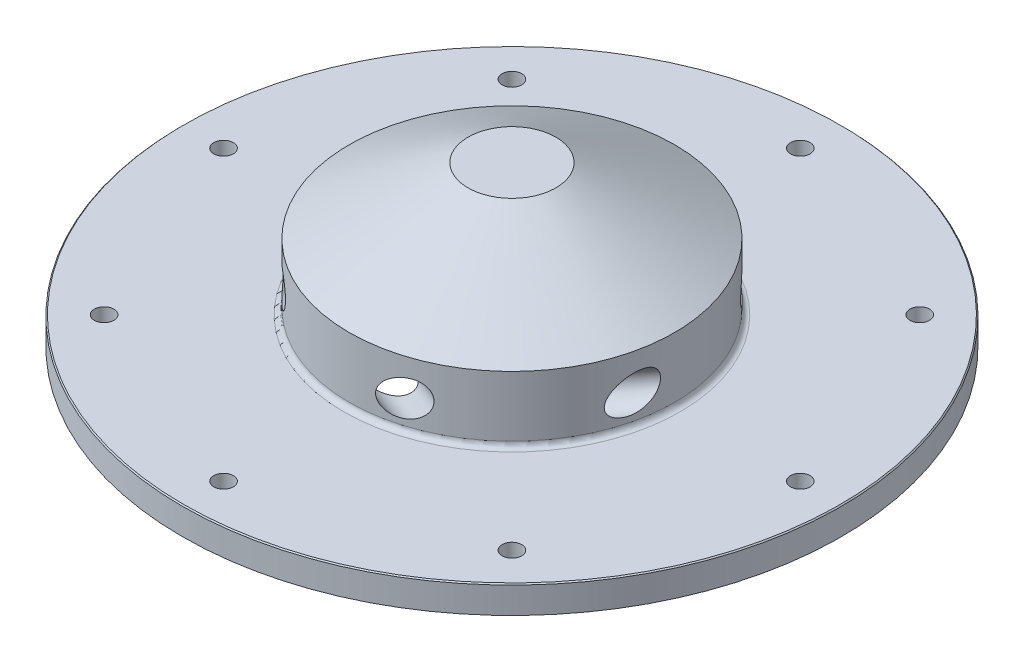
SolidWorks part; units mm, degrees
material "7075-T6 (SN)"
ref_plane "Front Plane" through (0, 0, 0) normal (0, 0, 1) x (1, 0, 0)
ref_plane "Top Plane" through (0, 0, 0) normal (0, 1, 0) x (1, 0, 0)
ref_plane "Right Plane" through (0, 0, 0) normal (1, 0, 0) x (0, 0, -1)
sketch "Sketch2" plane through (0, 0, 0) normal (0, 1, 0) x (1, 0, 0)
  circle A0 centre (0, 0) radius 38.1
  dimension "D1" = 76.2
extrude "Boss-Extrude1" add sketch "Sketch2" along normal blind 3.175
hole_wizard "Tap Drill for #4-40 Tap1" positions "Sketch3" profile "Sketch4" hole size "#4-40" standard "ANSI Inch" end condition through all
sketch "Sketch3" plane through (0, 0, 0) normal (0, -1, 0) x (-1, 0, 0)
  point P0 (0, -33.3375)
  dimension "D1" = 33.3375
sketch "Sketch4" plane through (0, 0, 33.3375) normal (1, 0, 0) x (0, 0, -1)
  line L0 (0, 0) -> (0, 3.175)
  line L1 (0, 3.175) -> (1.1303, 3.175)
  line L2 (1.1303, 3.175) -> (1.1303, 0)
  line L5 (1.1303, 0) -> (0, 0)
  line L11 (0, -6.35) -> (0, 107.95) construction
  dimension "Thru Hole Dia." = 2.2606
  dimension "Thru Hole Depth" = 3.175
pattern_circular "CirPattern1" count 8 over 360 about axis through (0, 0, 0) along (0, 1, 0) of "Tap Drill for #4-40 Tap1"
sketch "Sketch5" plane through (0, 3.175, 0) normal (0, 1, 0) x (1, 0, 0)
  circle A0 centre (0, 0) radius 28.575
  dimension "D1" = 57.15
sketch "Sketch7" plane through (0, 3.175, 0) normal (0, 1, 0) x (1, 0, 0)
  circle A0 centre (0, 0) radius 18.81
  dimension "D1" = 37.62
extrude "Boss-Extrude2" add sketch "Sketch7" along normal blind 7.62
sketch "Sketch8" plane through (0, 0, 0) normal (0, -1, 0) x (1, 0, 0)
  circle A0 centre (0, 0) radius 15
  dimension "D1" = 30
extrude "Cut-Extrude1" cut sketch "Sketch8" against normal blind 8.89
sketch "Sketch13" plane through (0, 10.795, 0) normal (0, 1, 0) x (1, 0, 0)
  circle A0 centre (0, 0) radius 18.81
  circle A1 centre (0, 0) radius 18.81 construction
  dimension "D1" = 0
ref_plane "Plane2" through (0, 18.415, 0) normal (0, 1, 0) x (1, 0, 0)
sketch "Sketch14" plane through (0, 18.415, 0) normal (0, 1, 0) x (1, 0, 0)
  circle A0 centre (0, 0) radius 5.08
  dimension "D1" = 10.16
loft "Loft2" add profiles "Sketch14", "Sketch13" connector at (-0.0647, 18.415, 5.0796) connector at (0, 10.795, 18.81)
fillet "Fillet1" radius 0.635 1 edges at (0, 8.89, -15)
chamfer "Chamfer1" distance 0.127 angle 45 1 edges at (0, 3.175, 38.1)
ref_plane "Plane4" through (0, 7.62, 0) normal (0, 1, 0) x (1, 0, 0)
fillet "Fillet2" radius 0.635 1 edges at (0, 3.175, 18.81)
ref_axis "Axis1" through (41.91, 7.62, 0) along (-1, 0, 0)
ref_plane "Plane3" through (0, 0.5104, 1.905) normal (0, 0.2588, 0.9659) x (-1, 0, 0)
sketch "Sketch16" plane through (0, 0.5104, 1.905) normal (0, 0.2588, 0.9659) x (-1, 0, 0)
  circle A0 centre (12.71, -2.7899) radius 1.98
  dimension "D1" = 3.96
  dimension "D2" = 12.71
  dimension "D3" = 2.7899
extrude "Cut-Extrude2" cut sketch "Sketch16" along normal through all
pattern_circular "CirPattern2" count 6 over 360 about axis through (0, 10.795, 0) along (0, 1, 0) of "Cut-Extrude2"
